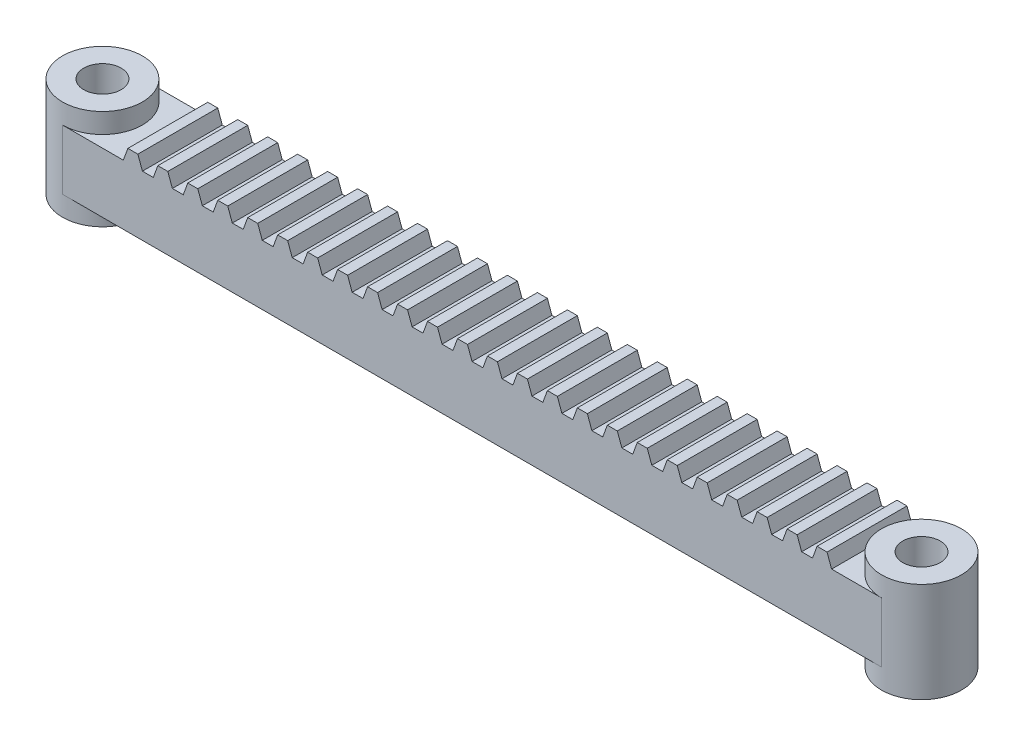
SolidWorks part; units mm, degrees
ref_plane "Front Plane" through (0, 0, 0) normal (0, 0, 1) x (1, 0, 0)
ref_plane "Top Plane" through (0, 0, 0) normal (0, 1, 0) x (1, 0, 0)
ref_plane "Right Plane" through (0, 0, 0) normal (1, 0, 0) x (0, 0, -1)
sketch "Sketch1" plane through (0, 0, 0) normal (0, 1, 0) x (1, 0, 0)
  line L1 (-2082.8, -203.2) -> (2082.8, -203.2)
  line L2 (-2082.8, -203.2) -> (-2082.8, 203.2)
  line L3 (-2082.8, 203.2) -> (2082.8, 203.2)
  line L4 (2082.8, -203.2) -> (2082.8, 203.2)
  line L5 (-2082.8, -203.2) -> (2082.8, 203.2) construction
  line L6 (-2082.8, 203.2) -> (2082.8, -203.2) construction
  circle A0 centre (-2082.8, 0) radius 203.2
  circle A1 centre (2082.8, 0) radius 203.2
  circle A2 centre (-2082.8, 0) radius 95.25
  circle A4 centre (2082.8, 0) radius 95.25
  point P0 (0, 0)
  dimension "D1" = 4165.6
  dimension "D2" = 190.5
  dimension "D3" = 406.4
  dimension "D4" = 190.5
extrude "Boss-Extrude1" add sketch "Sketch1" along normal mid plane 304.8 contours A1 L3 A0 L1 region at (0, 0, 0)
extrude "Boss-Extrude2" add sketch "Sketch1<4>" along normal mid plane 508 contours A4 L4 A1 | A2 L2 A0 | A2 L2 A0 | A1 | A4 region at (-2181.9425, 0, 0) region at (-1983.6575, 0, 0) region at (1983.6575, 0, 0)
sketch "Sketch1<4>" plane through (0, 0, 0) normal (0, 1, 0) x (1, 0, 0) same geometry as "Sketch1"
sketch "Sketch2" plane through (0, 0, 203.2) normal (0, 0, 1) x (1, 0, 0)
  line L0 (1828.8, 152.4) -> (1805.6879, 215.9)
  line L1 (-2082.8, 152.4) -> (2082.8, 152.4) construction
  line L2 (1805.6879, 215.9) -> (1754.8879, 215.9)
  line L3 (1754.8879, 215.9) -> (1731.7758, 152.4)
  line L4 (1780.2879, 215.9) -> (1780.2879, 152.4) construction
  line L5 (2286, -254) -> (2286, 254) construction
  line L6 (1731.7758, 152.4) -> (1828.8, 152.4)
  dimension "D1" = 40
  dimension "D2" = 457.2
  dimension "D3" = 50.8
  dimension "D4" = 63.5
extrude "Boss-Extrude3" add sketch "Sketch2" against normal up to surface (406.4 mm away) up to face at (0, 0, -203.2)
pattern_linear "LPattern1" count 24 spacing 152.4 along (-1, 0, 0) of "Boss-Extrude3"
